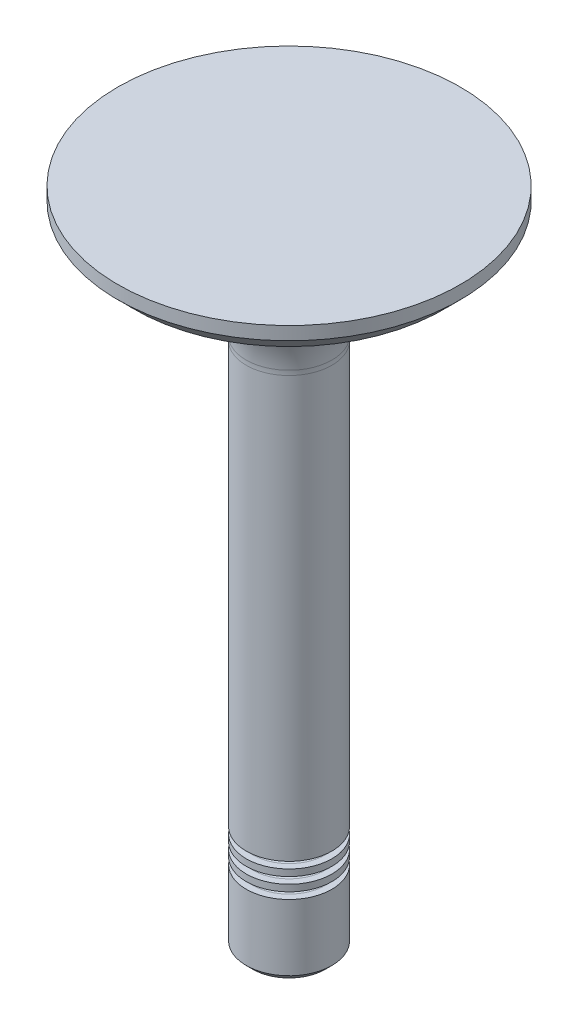
SolidWorks part; units mm, degrees
material "Silchrome I"
ref_plane "Front Plane" through (0, 0, 0) normal (0, 0, 1) x (1, 0, 0)
ref_plane "Top Plane" through (0, 0, 0) normal (0, 1, 0) x (1, 0, 0)
ref_plane "Right Plane" through (0, 0, 0) normal (1, 0, 0) x (0, 0, -1)
sketch "Sketch1" plane through (0, 0, 0) normal (0, 0, 1) x (1, 0, 0)
  line L0 (0, 224.083) -> (0, 124.083) construction
  line L1 (0, 224.083) -> (-25.92, 224.083)
  line L2 (-25.92, 224.083) -> (-25.92, 222.083)
  line L3 (-25.92, 222.083) -> (-23.328, 219.491)
  line L5 (-6.48, 204.053) -> (-6.48, 124.083)
  line L6 (-6.48, 124.083) -> (0, 124.083)
  line L7 (0, 224.083) -> (0, 124.083)
  arc A3 (-23.328, 219.491) -> (-6.48, 204.053) centre (-22.623, 203.348) cw
  dimension "D1" = 25.92
  dimension "D2" = 45
  dimension "D4" = 6.48
  dimension "D5" = 18.03
  dimension "D7" = 100
  dimension "D3" = 2.592
  dimension "D6" = 2
revolve "Revolve1" add sketch "Sketch1" angle 360 about L0
fillet "Fillet1" radius 10 1 edges at (-6.48, 204.053, 0)
chamfer "Chamfer1" distance 1 angle 45 1 edges at (-6.48, 124.083, 0)
sketch "Sketch5" plane through (0, 0, 0) normal (1, 0, 0) x (0, 0, -1)
  line L3 (-7.48, 138.083) -> (-5.48, 138.083)
  line L4 (0, 203.7831) -> (0, 125.083) construction
  line L5 (6.48, 203.7831) -> (-6.48, 203.7831) construction
  line L6 (6.48, 125.083) -> (-6.48, 125.083) construction
  line L7 (-7.48, 137.083) -> (-5.48, 137.083)
  line L8 (-7.48, 135.083) -> (-5.48, 135.083)
  line L9 (-7.48, 135.083) -> (-7.48, 136.083)
  line L10 (-7.48, 136.083) -> (-5.48, 136.083)
  line L12 (-7.48, 137.083) -> (-7.48, 138.083)
  line L13 (-7.48, 140.083) -> (-5.48, 140.083)
  line L14 (-7.48, 139.083) -> (-5.48, 139.083)
  line L15 (-7.48, 139.083) -> (-7.48, 140.083)
  arc A0 (-5.48, 135.083) -> (-5.48, 136.083) centre (-5.48, 135.583) ccw
  arc A1 (-5.48, 137.083) -> (-5.48, 138.083) centre (-5.48, 137.583) ccw
  arc A2 (-5.48, 139.083) -> (-5.48, 140.083) centre (-5.48, 139.583) ccw
  point P10 (-6.48, 135.583)
  dimension "D1" = 1
  dimension "D2" = 1
  dimension "D6" = 10
  dimension "D7" = 12
  dimension "D3" = 3
revolve "Cut-Revolve2" cut sketch "Sketch5" angle 360 about L4
sketch "Sketch6" plane through (0, 0, 0) normal (0, 0, 1) x (1, 0, 0)
  line L0 (0, 224.083) -> (0, 93.6363) construction
  line L1 (25.92, 224.083) -> (-25.92, 224.083) construction
  point P3 (0, 0)
  point P6 (0, 93.6363)
equation "\"Valve Diameter\"= 51.84mm"
equation "\"Seat Angle Beta\"= 45deg"
equation "\"Seat Diameter\"= 46.656mm"
equation "\"Stem Diameter\"= 12.96mm"
equation "\"Max Lift\"= 18.03mm"
equation "\"Seat Width\"= 2.592mm"
equation "\"D1@Sketch1\"=\"Valve Diameter\"/2"
equation "\"D2@Sketch1\"=\"Seat Angle Beta\""
equation "\"D5@Sketch1\"=\"Max Lift\""
equation "\"Head Thickness\"= 2mm"
equation "\"Overall Length\"= 100mm"
equation "\"D7@Sketch1\"=\"Overall Length\""
equation "\"D3@Sketch1\"=\"Seat Width\""
equation "\"D6@Sketch1\"=\"Head Thickness\""
